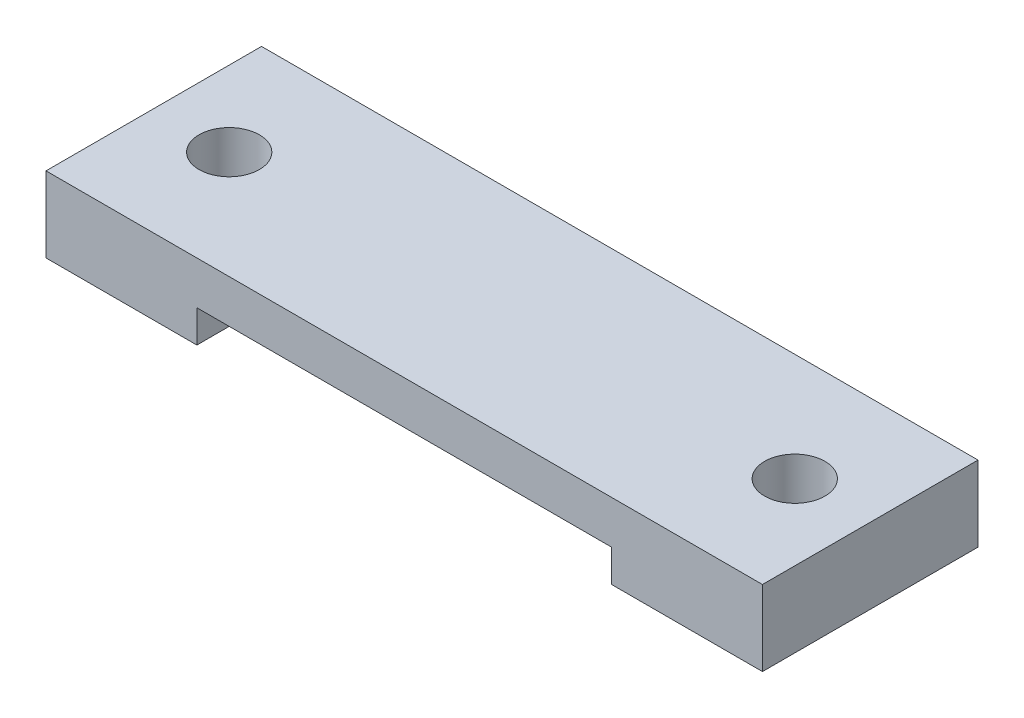
SolidWorks part; units mm, degrees
ref_plane "Front Plane" through (0, 0, 0) normal (0, 0, 1) x (1, 0, 0)
ref_plane "Top Plane" through (0, 0, 0) normal (0, 1, 0) x (1, 0, 0)
ref_plane "Right Plane" through (0, 0, 0) normal (1, 0, 0) x (0, 0, -1)
sketch "Sketch1" plane through (0, 0, 0) normal (0, 1, 0) x (1, 0, 0)
  line L0 (-55, 0) -> (55, 0) construction
  line L1 (-9.62, -5) -> (9.62, -5)
  line L2 (-9.62, -5) -> (-9.62, 5)
  line L3 (-9.62, 5) -> (9.62, 5)
  line L4 (9.62, -5) -> (9.62, 5)
  line L5 (-9.62, -5) -> (9.62, 5) construction
  line L6 (-9.62, 5) -> (9.62, -5) construction
  line L7 (-9.62, 5) -> (-16.62, 5)
  line L8 (-9.62, 5) -> (-9.62, -5)
  line L9 (-9.62, -5) -> (-16.62, -5)
  line L10 (-16.62, 5) -> (-16.62, -5)
  line L11 (9.62, 5) -> (16.62, 5)
  line L12 (9.62, 5) -> (9.62, -5)
  line L13 (9.62, -5) -> (16.62, -5)
  line L14 (16.62, 5) -> (16.62, -5)
  circle A0 centre (-13.12, 0) radius 1.4
  circle A1 centre (13.12, 0) radius 1.4
  point P0 (0, 0)
  dimension "D4" = 2.8
  dimension "D1" = 19.24
  dimension "D2" = 10
  dimension "D3" = 7
  dimension "D5" = 3.5
  dimension "D6" = 3.5
extrude "Boss-Extrude1" add sketch "Sketch1" against normal blind 3.5 contours L7 L10 L9 L2 A0 | L14 L11 L4 L13 A1 region at (-13.12, 0, 4.8779) region at (9.7421, 0, 0)
extrude "Boss-Extrude2" add sketch "Sketch1<3>" against normal blind 2 contours L1 L4 L3 L2 region at (0, 0, 0)
sketch "Sketch1<3>" plane through (0, 0, 0) normal (0, 1, 0) x (1, 0, 0) same geometry as "Sketch1"
